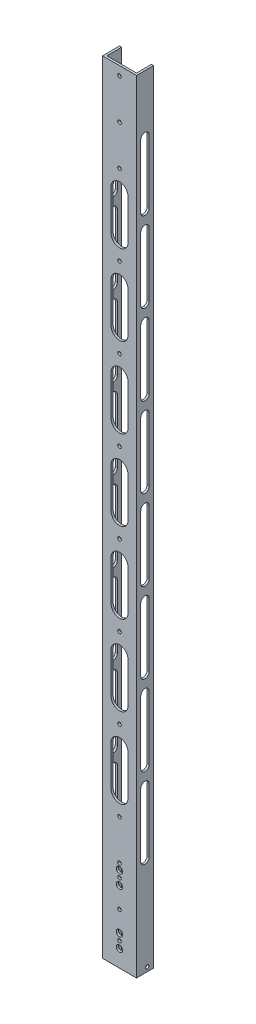
SolidWorks part; units mm, degrees
material "6061-T6 (SS)"
ref_plane "Front" through (0, 0, 0) normal (0, 0, 1) x (1, 0, 0)
ref_plane "Top" through (0, 0, 0) normal (0, 1, 0) x (1, 0, 0)
ref_plane "Right" through (0, 0, 0) normal (1, 0, 0) x (0, 0, -1)
sketch "Sketch1" plane through (0, 0, 0) normal (0, 1, 0) x (1, 0, 0)
  line L0 (3.175, 3.175) -> (3.175, 25.4)
  line L1 (0, 0) -> (50.8, 0)
  line L2 (0, 0) -> (0, 25.4)
  line L4 (50.8, 0) -> (50.8, 25.4)
  line L5 (3.175, 3.175) -> (47.625, 3.175)
  line L6 (47.625, 3.175) -> (47.625, 25.4)
  line L7 (0, 25.4) -> (3.175, 25.4)
  line L8 (50.8, 25.4) -> (47.625, 25.4)
  dimension "D1" = 25.4
  dimension "D2" = 50.8
  dimension "D3" = 3.175
extrude "Boss-Extrude1" add sketch "Sketch1" along normal blind 1168.4
sketch "Sketch2" plane through (0, 0, 0) normal (0, 0, 1) x (1, 0, 0)
  line L0 (25.4, 0) -> (25.4, 76.2) construction
  line L1 (0, 0) -> (50.8, 0) construction
  circle A0 centre (25.4, 76.2) radius 2.667
  circle A1 centre (25.4, 136.144) radius 2.667
  circle A2 centre (25.4, 196.088) radius 2.667
  circle A3 centre (25.4, 256.032) radius 2.667
  circle A4 centre (25.4, 315.976) radius 2.667
  circle A5 centre (25.4, 375.92) radius 2.667
  circle A6 centre (25.4, 435.864) radius 2.667
  circle A7 centre (25.4, 495.808) radius 2.667
  circle A8 centre (25.4, 555.752) radius 2.667
  circle A11 centre (25.4, 615.696) radius 2.667
  circle A12 centre (25.4, 675.64) radius 2.667
  circle A13 centre (25.4, 735.584) radius 2.667
  circle A14 centre (25.4, 795.528) radius 2.667
  circle A15 centre (25.4, 855.472) radius 2.667
  circle A16 centre (25.4, 915.416) radius 2.667
  circle A17 centre (25.4, 975.36) radius 2.667
  circle A18 centre (25.4, 1035.304) radius 2.667
  circle A19 centre (25.4, 1095.248) radius 2.667
  circle A20 centre (25.4, 1155.192) radius 2.667
  dimension "D2" = 5.334
  dimension "D1" = 76.2
  dimension "D3" = 19
extrude "Igus_Holes" cut sketch "Sketch2" against normal up to next
sketch "Sketch3" plane through (0, 0, -3.175) normal (0, 0, -1) x (-1, 0, 0)
  line L0 (-25.4, 0) -> (-25.4, 25.4) construction
  line L1 (-47.625, 0) -> (-3.175, 0) construction
  circle A0 centre (-25.4, 25.4) radius 4.7625
  circle A8 centre (-25.4, 35.4) radius 2.667
  circle A9 centre (-25.4, 117) radius 2.667
  circle A10 centre (-25.4, 45.4) radius 4.7625 construction
  circle A11 centre (-25.4, 45.4) radius 4.7625
  circle A12 centre (-25.4, 107) radius 4.7625 construction
  circle A13 centre (-25.4, 107) radius 4.7625
  circle A14 centre (-25.4, 127) radius 4.7625 construction
  circle A15 centre (-25.4, 127) radius 4.7625
  dimension "D2" = 9.525
  dimension "D4" = 5.334
  dimension "D3" = 5.334
  dimension "D1" = 25.4
extrude "Cut-Extrude2" cut sketch "Sketch3" against normal up to next
sketch "Sketch4" plane through (0, 0, 0) normal (-1, 0, 0) x (0, 0, 1)
  line L0 (-15.875, 0) -> (-15.875, 6.35) construction
  line L2 (-25.4, 0) -> (0, 0) construction
  line L3 (-15.875, 6.35) -> (-25.4, 6.35) construction
  line L4 (-25.4, 1168.4) -> (-25.4, 0) construction
  circle A0 centre (-15.875, 6.35) radius 2.667
  dimension "D2" = 5.334
  dimension "D1" = 6.35
  dimension "D3" = 9.525
extrude "Cut-Extrude3" cut sketch "Sketch4" against normal through all
ref_plane "Mid_Plane" through (25.4, 0, 0) normal (1, 0, 0) x (0, 0, -1)
sketch "Sketch5" plane through (0, 0, 0) normal (0, 0, 1) x (1, 0, 0)
  line L0 (25.4, 1005.36) -> (25.4, 945.36) construction
  line L1 (38.1, 1005.36) -> (38.1, 945.36)
  line L2 (12.7, 1005.36) -> (12.7, 945.36)
  line L4 (0, 1168.4) -> (0, 0) construction
  line L5 (25.4, 885.472) -> (25.4, 825.472) construction
  line L6 (38.1, 885.472) -> (38.1, 825.472)
  line L7 (12.7, 885.472) -> (12.7, 825.472)
  line L8 (25.4, 765.584) -> (25.4, 705.584) construction
  line L9 (38.1, 765.584) -> (38.1, 705.584)
  line L10 (12.7, 765.584) -> (12.7, 705.584)
  line L11 (25.4, 645.696) -> (25.4, 585.696) construction
  line L12 (38.1, 645.696) -> (38.1, 585.696)
  line L13 (12.7, 645.696) -> (12.7, 585.696)
  line L14 (25.4, 525.808) -> (25.4, 465.808) construction
  line L15 (38.1, 525.808) -> (38.1, 465.808)
  line L16 (12.7, 525.808) -> (12.7, 465.808)
  line L17 (25.4, 405.92) -> (25.4, 345.92) construction
  line L18 (38.1, 405.92) -> (38.1, 345.92)
  line L19 (12.7, 405.92) -> (12.7, 345.92)
  line L20 (25.4, 286.032) -> (25.4, 226.032) construction
  line L21 (38.1, 286.032) -> (38.1, 226.032)
  line L22 (12.7, 286.032) -> (12.7, 226.032)
  arc A0 (38.1, 1005.36) -> (12.7, 1005.36) centre (25.4, 1005.36) ccw
  arc A1 (12.7, 945.36) -> (38.1, 945.36) centre (25.4, 945.36) ccw
  circle A2 centre (25.4, 975.36) radius 2.667 construction
  circle A3 centre (25.4, 975.36) radius 2.667 construction
  arc A4 (38.1, 885.472) -> (12.7, 885.472) centre (25.4, 885.472) ccw
  arc A5 (12.7, 825.472) -> (38.1, 825.472) centre (25.4, 825.472) ccw
  arc A6 (38.1, 765.584) -> (12.7, 765.584) centre (25.4, 765.584) ccw
  arc A7 (12.7, 705.584) -> (38.1, 705.584) centre (25.4, 705.584) ccw
  arc A8 (38.1, 645.696) -> (12.7, 645.696) centre (25.4, 645.696) ccw
  arc A9 (12.7, 585.696) -> (38.1, 585.696) centre (25.4, 585.696) ccw
  arc A10 (38.1, 525.808) -> (12.7, 525.808) centre (25.4, 525.808) ccw
  arc A11 (12.7, 465.808) -> (38.1, 465.808) centre (25.4, 465.808) ccw
  arc A12 (38.1, 405.92) -> (12.7, 405.92) centre (25.4, 405.92) ccw
  arc A13 (12.7, 345.92) -> (38.1, 345.92) centre (25.4, 345.92) ccw
  arc A14 (38.1, 286.032) -> (12.7, 286.032) centre (25.4, 286.032) ccw
  arc A15 (12.7, 226.032) -> (38.1, 226.032) centre (25.4, 226.032) ccw
  point P2 (25.4, 975.36)
  point P16 (25.4, 855.472)
  point P23 (25.4, 735.584)
  point P30 (25.4, 615.696)
  point P37 (25.4, 495.808)
  point P44 (25.4, 375.92)
  point P51 (25.4, 256.032)
  dimension "D3" = 30
  dimension "D4" = 30
  dimension "D1" = 25.4
  dimension "D2" = 12.7
extrude "Back_Cuts" cut sketch "Sketch5" against normal up to next
sketch "Sketch6" plane through (0, 0, 0) normal (-1, 0, 0) x (0, 0, 1)
  line L0 (-12.7, 1082.05) -> (-12.7, 987.25) construction
  line L1 (-6.35, 1082.05) -> (-6.35, 987.25)
  line L2 (-19.05, 1082.05) -> (-19.05, 987.25)
  line L3 (-25.4, 1168.4) -> (-25.4, 0) construction
  line L4 (-25.4, 1168.4) -> (0, 1168.4) construction
  line L5 (-12.7, 962.05) -> (-12.7, 867.25) construction
  line L6 (-6.35, 962.05) -> (-6.35, 867.25)
  line L7 (-19.05, 962.05) -> (-19.05, 867.25)
  line L8 (-12.7, 842.05) -> (-12.7, 747.25) construction
  line L9 (-6.35, 842.05) -> (-6.35, 747.25)
  line L10 (-19.05, 842.05) -> (-19.05, 747.25)
  line L11 (-12.7, 722.05) -> (-12.7, 627.25) construction
  line L12 (-6.35, 722.05) -> (-6.35, 627.25)
  line L13 (-19.05, 722.05) -> (-19.05, 627.25)
  line L14 (-12.7, 602.05) -> (-12.7, 507.25) construction
  line L15 (-6.35, 602.05) -> (-6.35, 507.25)
  line L16 (-19.05, 602.05) -> (-19.05, 507.25)
  line L17 (-12.7, 482.05) -> (-12.7, 387.25) construction
  line L18 (-6.35, 482.05) -> (-6.35, 387.25)
  line L19 (-19.05, 482.05) -> (-19.05, 387.25)
  line L20 (-12.7, 362.05) -> (-12.7, 267.25) construction
  line L21 (-6.35, 362.05) -> (-6.35, 267.25)
  line L22 (-19.05, 362.05) -> (-19.05, 267.25)
  line L23 (-12.7, 242.05) -> (-12.7, 147.25) construction
  line L24 (-6.35, 242.05) -> (-6.35, 147.25)
  line L25 (-19.05, 242.05) -> (-19.05, 147.25)
  arc A0 (-6.35, 1082.05) -> (-19.05, 1082.05) centre (-12.7, 1082.05) ccw
  arc A1 (-19.05, 987.25) -> (-6.35, 987.25) centre (-12.7, 987.25) ccw
  arc A2 (-6.35, 962.05) -> (-19.05, 962.05) centre (-12.7, 962.05) ccw
  arc A3 (-19.05, 867.25) -> (-6.35, 867.25) centre (-12.7, 867.25) ccw
  arc A4 (-6.35, 842.05) -> (-19.05, 842.05) centre (-12.7, 842.05) ccw
  arc A5 (-19.05, 747.25) -> (-6.35, 747.25) centre (-12.7, 747.25) ccw
  arc A6 (-6.35, 722.05) -> (-19.05, 722.05) centre (-12.7, 722.05) ccw
  arc A7 (-19.05, 627.25) -> (-6.35, 627.25) centre (-12.7, 627.25) ccw
  arc A8 (-6.35, 602.05) -> (-19.05, 602.05) centre (-12.7, 602.05) ccw
  arc A9 (-19.05, 507.25) -> (-6.35, 507.25) centre (-12.7, 507.25) ccw
  arc A10 (-6.35, 482.05) -> (-19.05, 482.05) centre (-12.7, 482.05) ccw
  arc A11 (-19.05, 387.25) -> (-6.35, 387.25) centre (-12.7, 387.25) ccw
  arc A12 (-6.35, 362.05) -> (-19.05, 362.05) centre (-12.7, 362.05) ccw
  arc A13 (-19.05, 267.25) -> (-6.35, 267.25) centre (-12.7, 267.25) ccw
  arc A14 (-6.35, 242.05) -> (-19.05, 242.05) centre (-12.7, 242.05) ccw
  arc A15 (-19.05, 147.25) -> (-6.35, 147.25) centre (-12.7, 147.25) ccw
  point P2 (-12.7, 1034.65)
  point P7 (-12.7, 1088.4)
  point P8 (-12.7, 980.9)
  point P17 (-12.7, 914.65)
  point P24 (-12.7, 794.65)
  point P29 (-12.7, 674.65)
  point P36 (-12.7, 554.65)
  point P43 (-12.7, 434.65)
  point P50 (-12.7, 314.65)
  point P57 (-12.7, 194.65)
  point P62 (-12.7, 968.4)
  dimension "D1" = 12.7
  dimension "D2" = 107.5
  dimension "D3" = 6.35
  dimension "D4" = 80
  dimension "D6" = 12.5
  dimension "D5" = 8
extrude "Cut-Extrude5" cut sketch "Sketch6" against normal through all
sketch "Sketch7" plane through (0, 0, 0) normal (0, 0, 1) x (1, 0, 0)
  line L0 (28.067, 196.088) -> (50.8, 196.088) construction
  line L1 (50.8, 1168.4) -> (50.8, 0) construction
  line L2 (22.733, 196.088) -> (0, 196.088) construction
  line L3 (0, 1168.4) -> (0, 0) construction
  circle A0 centre (25.4, 196.088) radius 2.667 construction
sketch "Sketch8" plane through (0, 0, 0) normal (-1, 0, 0) x (0, 0, 1)
  line L0 (0, 196.088) -> (-6.35, 196.088) construction
  line L1 (-6.35, 147.25) -> (-6.35, 242.05) construction
